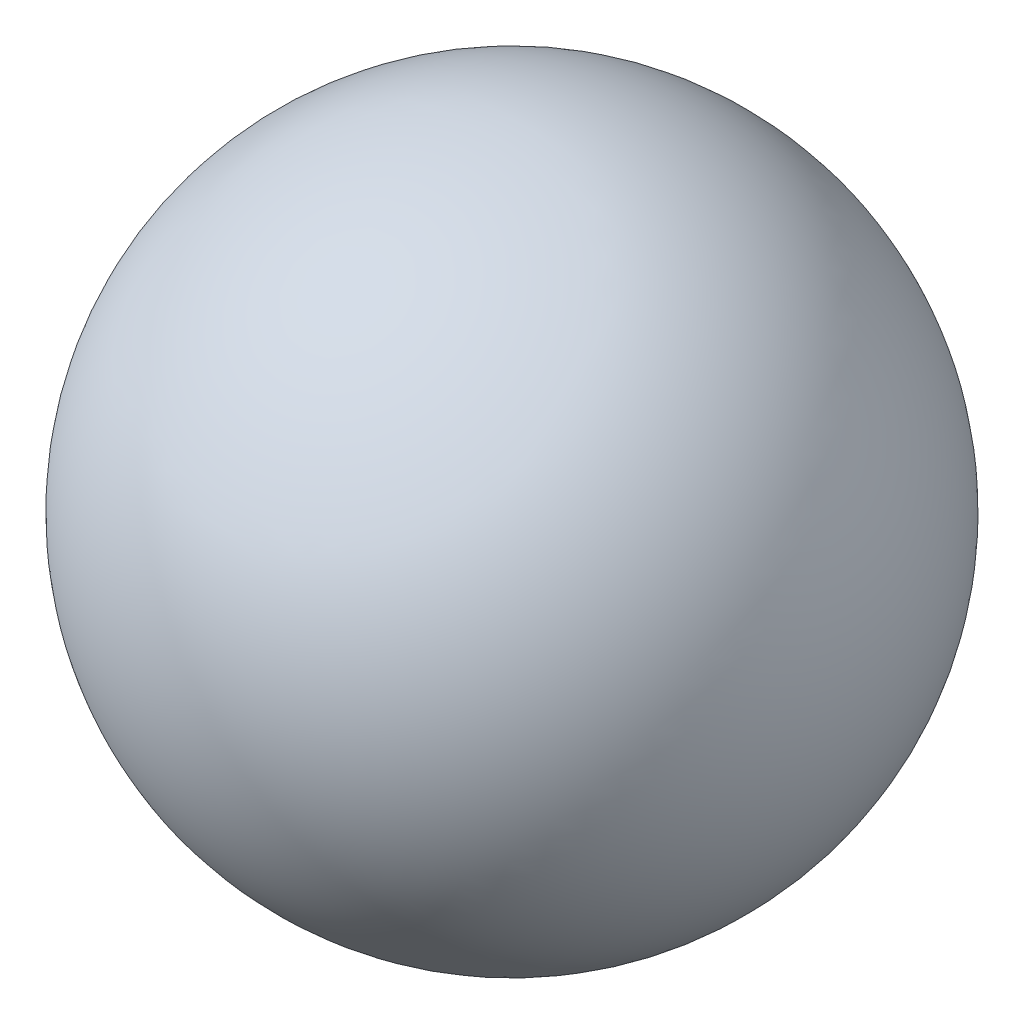
SolidWorks part; units mm, degrees
ref_plane "Спереди" through (0, 0, 0) normal (0, 0, 1) x (1, 0, 0)
ref_plane "Сверху" through (0, 0, 0) normal (0, 1, 0) x (1, 0, 0)
ref_plane "Справа" through (0, 0, 0) normal (1, 0, 0) x (0, 0, -1)
sketch "Эскиз3" [suppressed] plane through (0, 0, 0) normal (0, 0, 1) x (1, 0, 0)
  line L0 (0, 4.75) -> (0, -4.75)
  arc A0 (0, -4.75) -> (0, 4.75) centre (0, 0) ccw
  dimension "D1" = 4.75
revolve "Шарик 9мм" [suppressed] add sketch "Эскиз3" angle 360 about L0
sketch "Эскиз1" plane through (0, 0, 0) normal (0, 0, 1) x (1, 0, 0)
  line L0 (0, 4.5) -> (0, -4.5)
  arc A0 (0, -4.5) -> (0, 4.5) centre (0, 0) ccw
  dimension "D1" = 4.5
revolve "Шарик 9,5мм" [suppressed] add sketch "Эскиз1" angle 360 about L0
sketch "Эскиз4" [suppressed] plane through (0, 0, 0) normal (0, 0, 1) x (1, 0, 0)
  line L0 (0, 5) -> (0, -5)
  arc A0 (0, -5) -> (0, 5) centre (0, 0) ccw
  dimension "D1" = 5
revolve "шарик 10мм" [suppressed] add sketch "Эскиз4" angle 360 about L0
sketch "Эскиз5" [suppressed] plane through (0, 0, 0) normal (0, 0, 1) x (1, 0, 0)
  line L1 (0, 6) -> (0, -6)
  arc A1 (0, -6) -> (0, 6) centre (0, 0) ccw
  dimension "D1" = 6
revolve "Шарик 12мм" [suppressed] add sketch "Эскиз5" angle 360 about L1
sketch "Эскиз7" [suppressed] plane through (0, 0, 0) normal (0, 0, 1) x (1, 0, 0)
  line L0 (0, 7) -> (0, -7)
  arc A0 (0, 7) -> (0, -7) centre (0, 0) cw
  dimension "D1" = 7
revolve "Шарик 14мм" [suppressed] add sketch "Эскиз7" angle 360 about L0
sketch "Эскиз8" plane through (0, 0, 0) normal (0, 1, 0) x (1, 0, 0)
  line L0 (0, 7.25) -> (0, -7.25)
  arc A0 (0, 7.25) -> (0, -7.25) centre (0, 0) cw
  dimension "D1" = 7.25
revolve "Шарик 14.5мм" add sketch "Эскиз8" angle 360 about L0
